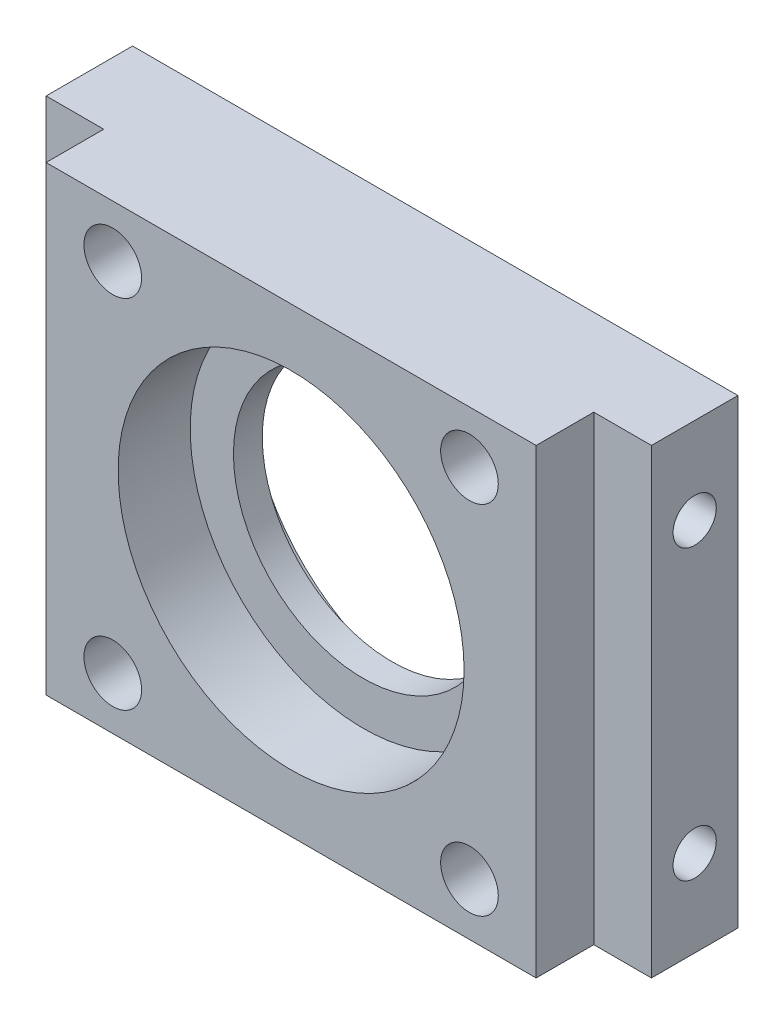
SolidWorks part; units mm, degrees
ref_plane "前视基准面" through (0, 0, 0) normal (0, 0, 1) x (1, 0, 0)
ref_plane "上视基准面" through (0, 0, 0) normal (0, 1, 0) x (1, 0, 0)
ref_plane "右视基准面" through (0, 0, 0) normal (1, 0, 0) x (0, 0, -1)
ref_plane "基准面1" through (0, 0, 10) normal (0, 0, 1) x (1, 0, 0)
sketch "草图1" plane through (0, 0, 10) normal (0, 0, 1) x (1, 0, 0)
  line L0 (21, 16) -> (-21, 16)
  line L1 (-21, 16) -> (-21, -16)
  line L2 (-21, -16) -> (21, -16)
  line L3 (21, -16) -> (21, 16)
extrude "凸台-拉伸1" add sketch "草图1" against normal blind 10
sketch "草图2" plane through (0, -16, 0) normal (0, -1, 0) x (1, 0, 0)
  line L0 (-21, 6) -> (-17, 6)
  line L1 (-17, 6) -> (-17, 10)
  line L2 (-17, 10) -> (-21, 10)
  line L3 (-21, 10) -> (-21, 6)
extrude "切除-拉伸1" cut sketch "草图2" against normal through all
sketch "草图3" plane through (0, -16, 0) normal (0, -1, 0) x (1, 0, 0)
  line L0 (21, 10) -> (17, 10)
  line L1 (17, 10) -> (17, 6)
  line L2 (17, 6) -> (21, 6)
  line L3 (21, 6) -> (21, 10)
extrude "切除-拉伸2" cut sketch "草图3" against normal through all
hole_wizard "Ø4.0 (4) 直径孔1" positions "草图5" profile "草图4" hole size "Ø4.0" standard "ANSI Metric"
sketch "草图5" plane through (0, 0, 10) normal (0, 0, 1) x (1, 0, 0)
  point P0 (12.3744, 12.3744)
  point P1 (12.3744, -12.3744)
  point P2 (-12.3744, -12.3744)
  point P3 (-12.3744, 12.3744)
sketch "草图4" plane through (12.3744, 12.3744, 10) normal (1, 0, 0) x (0, -1, 0)
  line L0 (0, 0) -> (0, 10)
  line L1 (0, 10) -> (2, 10)
  line L2 (2, 10) -> (2, 0)
  line L5 (2, 0) -> (0, 0)
  line L11 (0, -6.35) -> (0, 107.95) construction
  dimension "通孔孔直径" = 4
  dimension "通孔孔深度" = 10
hole_wizard "Ø3.0 (3) 直径孔1" positions "草图7" profile "草图6" hole size "Ø3.0" standard "ANSI Metric"
sketch "草图7" plane through (21, 0, 0) normal (1, 0, 0) x (0, 0, -1)
  point P0 (-3, -10)
  point P1 (-3, 10)
sketch "草图6" plane through (21, -10, 3) normal (0, 1, 0) x (0, 0, -1)
  line L0 (0, 0) -> (0, 6)
  line L1 (0, 6) -> (1.5, 6)
  line L2 (1.5, 6) -> (1.5, 0)
  line L5 (1.5, 0) -> (0, 0)
  line L10 (0, 6) -> (-1.5, 6) construction
  line L11 (0, -6.35) -> (0, 107.95) construction
  dimension "孔直径" = 3
  dimension "孔深度" = 6
  dimension "导头角度" = 180
hole_wizard "Ø3.0 (3) 直径孔2" positions "草图9" profile "草图8" hole size "Ø3.0" standard "ANSI Metric"
sketch "草图9" plane through (-21, 0, 0) normal (-1, 0, 0) x (0, 0, 1)
  point P0 (3, -10)
  point P1 (3, 10)
sketch "草图8" plane through (-21, -10, 3) normal (0, 1, 0) x (0, 0, 1)
  line L0 (0, 0) -> (0, 6)
  line L1 (0, 6) -> (1.5, 6)
  line L2 (1.5, 6) -> (1.5, 0)
  line L5 (1.5, 0) -> (0, 0)
  line L10 (0, 6) -> (-1.5, 6) construction
  line L11 (0, -6.35) -> (0, 107.95) construction
  dimension "孔直径" = 3
  dimension "孔深度" = 6
  dimension "导头角度" = 180
hole_wizard "M20 六角头螺栓的柱形沉头孔1" positions "草图11" profile "草图10" counterbore size "M20" standard "ANSI Metric"
sketch "草图11" plane through (0, 0, 10) normal (0, 0, 1) x (1, 0, 0)
  point P0 (0, 0)
sketch "草图10" plane through (0, 0, 10) normal (1, 0, 0) x (0, -1, 0)
  line L0 (0, 0) -> (0, 10)
  line L1 (0, 10) -> (11.5, 10)
  line L3 (11.5, 10) -> (11.5, 4)
  line L4 (11.5, 4) -> (12, 4)
  line L5 (12, 4) -> (12, 0)
  line L7 (12, 0) -> (0, 0)
  line L11 (0, -6.35) -> (0, 107.95) construction
  dimension "通孔孔直径" = 23
  dimension "通孔孔深度" = 10
  dimension "柱形沉头孔直径" = 24
  dimension "柱形沉头孔深度" = 4
sketch "草图12" plane through (0, 0, 0) normal (0, 0, -1) x (-1, 0, 0)
  circle A0 centre (0, 0) radius 9
  circle A1 centre (0, 0) radius 11.5
  dimension "D1" = 18
extrude "凸台-拉伸2" add sketch "草图12" against normal up to surface (6 mm away) up to face at (11.5, 0, 6)
sketch "草图13" plane through (0, 0, 10) normal (0, 0, 1) x (1, 0, 0)
  circle A0 centre (0, 0) radius 12
extrude "切除-拉伸3" cut sketch "草图13" against normal blind 5
sketch "草图14" plane through (0, 0, 0) normal (0, 0, -1) x (-1, 0, 0)
  circle A0 centre (0, 0) radius 13
  dimension "D1" = 26
extrude "切除-拉伸4" cut sketch "草图14" against normal blind 3
